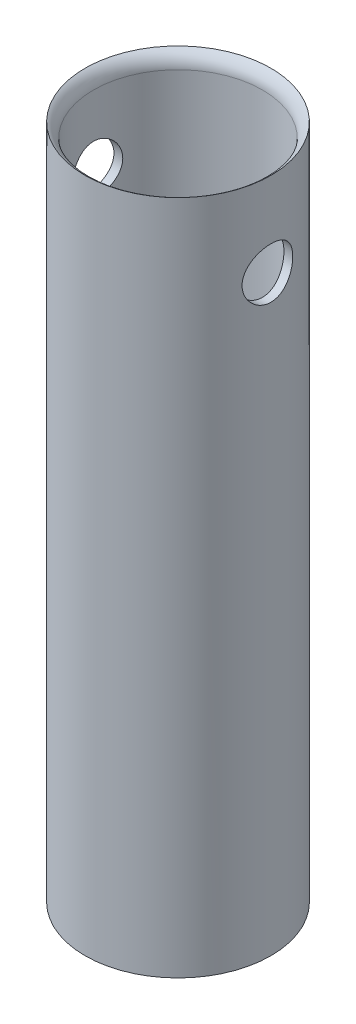
SolidWorks part; units mm, degrees
ref_plane "Front Plane" through (0, 0, 0) normal (0, 0, 1) x (1, 0, 0)
ref_plane "Top Plane" through (0, 0, 0) normal (0, 1, 0) x (1, 0, 0)
ref_plane "Right Plane" through (0, 0, 0) normal (1, 0, 0) x (0, 0, -1)
sketch "Sketch1" plane through (0, 0, 0) normal (0, 1, 0) x (1, 0, 0)
  circle A0 centre (0, 0) radius 5
  circle A1 centre (0, 0) radius 5.5
  dimension "D1" = 10
  dimension "D2" = 11
extrude "Boss-Extrude1" add sketch "Sketch1" along normal blind 40
fillet "Fillet1" radius 1 1 edges at (0, 40, 5)
fillet "Fillet2" radius 1 1 edges at (0, 0, 5)
sketch "Sketch2" plane through (0, 0, 0) normal (1, 0, 0) x (0, 0, -1)
  line L0 (-5.5, 40) -> (5.5, 40) construction
  circle A0 centre (0, 35) radius 1.5
  dimension "D2" = 3
  dimension "D1" = 5
extrude "Cut-Extrude1" cut sketch "Sketch2" against normal through all both and the other way through all
